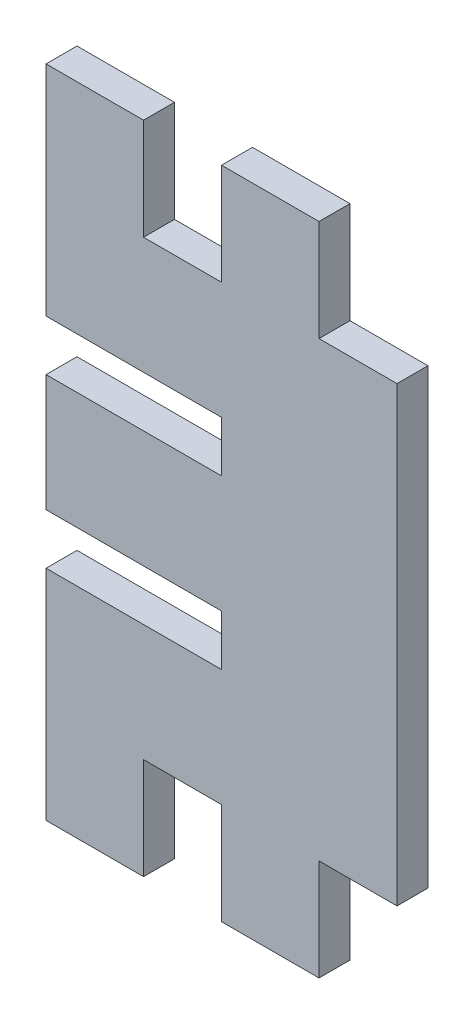
SolidWorks part; units mm, degrees
ref_plane "Front Plane" through (0, 0, 0) normal (0, 0, 1) x (1, 0, 0)
ref_plane "Top Plane" through (0, 0, 0) normal (0, 1, 0) x (1, 0, 0)
ref_plane "Right Plane" through (0, 0, 0) normal (1, 0, 0) x (0, 0, -1)
sketch "Sketch1" plane through (0, 0, 0) normal (0, 0, 1) x (1, 0, 0)
  line L0 (0, 0) -> (60.2571, 0) construction
  line L1 (55, 0) -> (-55, 0) construction
  line L2 (-18, -6) -> (-18, 6)
  line L3 (-18, 6) -> (0, 6)
  line L4 (0, 6) -> (0, 11.2)
  line L5 (0, 11.2) -> (-18, 11.2)
  line L6 (-18, 11.2) -> (-18, 33.6)
  line L7 (0, -55) -> (0, 55) construction
  line L8 (0, 1.5761) -> (0, 45.6913) construction
  line L9 (-18, 33.6) -> (-8, 33.6)
  line L10 (0, 33.6) -> (0, 23.2)
  line L11 (0, 23.2) -> (-8, 23.2)
  line L12 (-8, 23.2) -> (-8, 33.6)
  line L13 (0, 33.6) -> (10, 33.6)
  line L14 (10, 33.6) -> (10, 23.2)
  line L15 (10, 23.2) -> (18, 23.2)
  line L16 (18, 23.2) -> (18, -23.2)
  line L17 (-18, -6) -> (0, -6)
  line L18 (0, -6) -> (0, -11.2)
  line L19 (0, -11.2) -> (-18, -11.2)
  line L20 (-18, -11.2) -> (-18, -33.6)
  line L21 (0, -33.6) -> (0, -23.2)
  line L22 (-18, -33.6) -> (-8, -33.6)
  line L23 (10, -23.2) -> (18, -23.2)
  line L24 (10, -33.6) -> (10, -23.2)
  line L25 (0, -33.6) -> (10, -33.6)
  line L26 (-8, -23.2) -> (-8, -33.6)
  line L27 (0, -23.2) -> (-8, -23.2)
  line L28 (43.6365, 23.2) -> (43.537, 23.2)
  line L29 (0, -23.2) -> (0, -11.2) construction
  line L30 (0, -11.2) -> (-0.0397, -11.2018)
  point P23 (-18, 0)
  point P30 (18, 0)
  dimension "D1" = 36
  dimension "D2" = 5.2
  dimension "D3" = 10.4
  dimension "D4" = 12
  dimension "D5" = 10
  dimension "D6" = 12
  dimension "D7" = 8
extrude "Boss-Extrude2" add sketch "Sketch1" along normal blind 3.175 contours L27 L21 L25 L24 L23 L16 L15 L14 L13 L10 L11 L12 L9 L6 L5 L4 L3 L2 L17 L18 L19 L20 L22 L26 region at (0.011, 0, 0)
